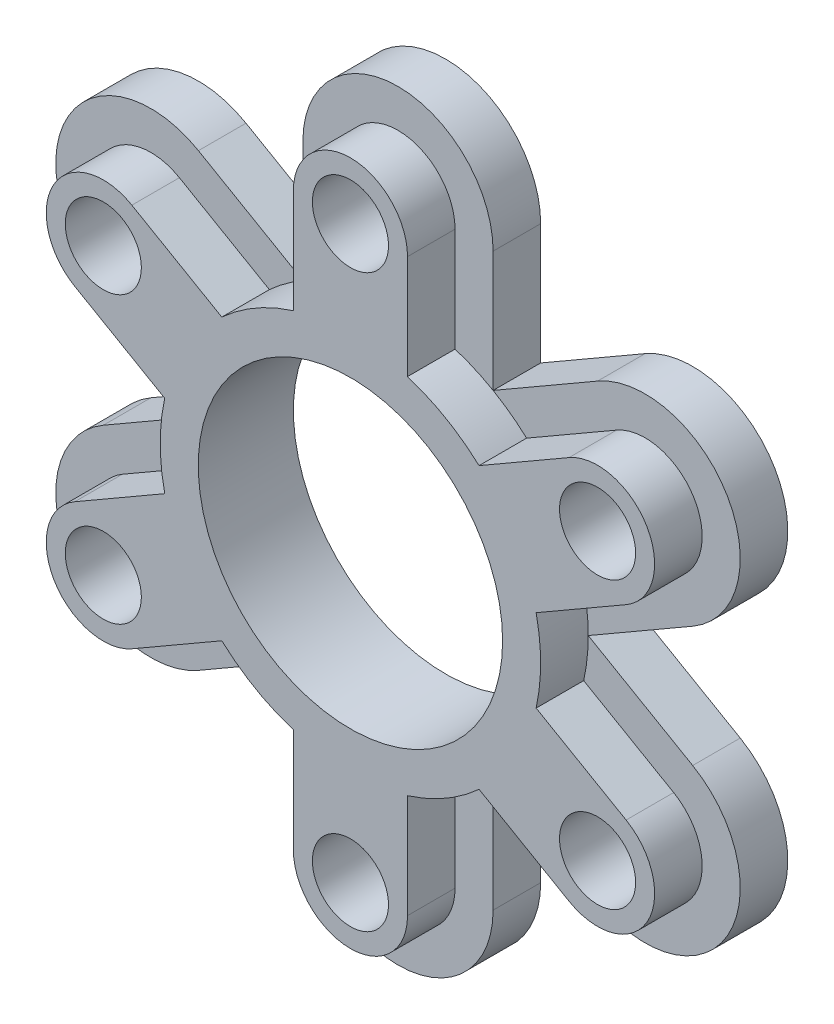
SolidWorks part; units mm, degrees
ref_plane "Front Plane" through (0, 0, 0) normal (0, 0, 1) x (1, 0, 0)
ref_plane "Top Plane" through (0, 0, 0) normal (0, 1, 0) x (1, 0, 0)
ref_plane "Right Plane" through (0, 0, 0) normal (1, 0, 0) x (0, 0, -1)
sketch "Sketch1" plane through (0, 0, 0) normal (0, 0, 1) x (1, 0, 0)
  line L0 (-50.8017, 0) -> (64.1892, 0) construction
  line L1 (-13.9585, 30) -> (15.1705, 30) construction
  line L2 (0, 48.8271) -> (0, -54.1094) construction
  line L3 (-10, 30) -> (-10, 17.3205)
  line L4 (-6, 30) -> (-6, 19.0788)
  line L5 (6, 30) -> (6, 19.0788)
  line L6 (22.9808, 20.1962) -> (13.5227, 14.7355)
  line L7 (10, 30) -> (10, 17.3205)
  line L8 (20.9808, 23.6603) -> (10, 17.3205)
  line L9 (28.9808, 9.8038) -> (19.5227, 4.3432)
  line L10 (30.9808, 6.3397) -> (20, 0)
  line L11 (28.9808, -9.8038) -> (19.5227, -4.3432)
  line L12 (30.9808, -6.3397) -> (20, 0)
  line L13 (22.9808, -20.1962) -> (13.5227, -14.7355)
  line L14 (20.9808, -23.6603) -> (10, -17.3205)
  line L15 (6, -30) -> (6, -19.0788)
  line L16 (10, -30) -> (10, -17.3205)
  line L17 (-6, -30) -> (-6, -19.0788)
  line L18 (-10, -30) -> (-10, -17.3205)
  line L19 (-22.9808, -20.1962) -> (-13.5227, -14.7355)
  line L20 (-20.9808, -23.6603) -> (-10, -17.3205)
  line L21 (-28.9808, -9.8038) -> (-19.5227, -4.3432)
  line L22 (-30.9808, -6.3397) -> (-20, 0)
  line L23 (-28.9808, 9.8038) -> (-19.5227, 4.3432)
  line L24 (-30.9808, 6.3397) -> (-20, 0)
  line L25 (-22.9808, 20.1962) -> (-13.5227, 14.7355)
  line L26 (-20.9808, 23.6603) -> (-10, 17.3205)
  circle A0 centre (0, 0) radius 30 construction
  circle A1 centre (0, 0) radius 16
  circle A2 centre (0, 30) radius 4
  arc A3 (10, 30) -> (-10, 30) centre (0, 30) ccw
  arc A5 (6, 30) -> (-6, 30) centre (0, 30) ccw
  arc A6 (30.9808, 6.3397) -> (20.9808, 23.6603) centre (25.9808, 15) ccw
  arc A7 (28.9808, 9.8038) -> (22.9808, 20.1962) centre (25.9808, 15) ccw
  circle A8 centre (25.9808, 15) radius 4
  arc A9 (20.9808, -23.6603) -> (30.9808, -6.3397) centre (25.9808, -15) ccw
  arc A10 (22.9808, -20.1962) -> (28.9808, -9.8038) centre (25.9808, -15) ccw
  circle A11 centre (25.9808, -15) radius 4
  arc A12 (-10, -30) -> (10, -30) centre (0, -30) ccw
  arc A13 (-6, -30) -> (6, -30) centre (0, -30) ccw
  circle A14 centre (0, -30) radius 4
  arc A15 (-30.9808, -6.3397) -> (-20.9808, -23.6603) centre (-25.9808, -15) ccw
  arc A16 (-28.9808, -9.8038) -> (-22.9808, -20.1962) centre (-25.9808, -15) ccw
  circle A17 centre (-25.9808, -15) radius 4
  arc A18 (-20.9808, 23.6603) -> (-30.9808, 6.3397) centre (-25.9808, 15) ccw
  arc A19 (-22.9808, 20.1962) -> (-28.9808, 9.8038) centre (-25.9808, 15) ccw
  circle A20 centre (-25.9808, 15) radius 4
  arc A21 (-19.5227, 4.3432) -> (-19.5227, -4.3432) centre (0, 0) ccw
  arc A22 (-13.5227, -14.7355) -> (-6, -19.0788) centre (0, 0) ccw
  arc A23 (6, -19.0788) -> (13.5227, -14.7355) centre (0, 0) ccw
  arc A24 (19.5227, -4.3432) -> (19.5227, 4.3432) centre (0, 0) ccw
  arc A25 (13.5227, 14.7355) -> (6, 19.0788) centre (0, 0) ccw
  arc A26 (-6, 19.0788) -> (-13.5227, 14.7355) centre (0, 0) ccw
  dimension "D1" = 60
  dimension "D2" = 32
  dimension "D3" = 8
  dimension "D4" = 10
  dimension "D5" = 6
  dimension "D6" = 6
  dimension "D7" = 20
extrude "Boss-Extrude2" add sketch "Sketch1" along normal blind 10 contours L4 A26 L25 A19 L23 A21 L21 A16 L19 A22 L17 A13 L15 A23 L13 A10 L11 A24 L9 A7 L6 A25 L5 A5 A20 A1 A2 A8 A11 A14 A17 region at (-7.6606, 17.4276, 0)
extrude "Boss-Extrude3" add sketch "Sketch1<4>" along normal blind 5 contours A26 L26 A18 L24 A21 L23 A19 L25 | A26 L4 A5 L5 A25 L7 A3 L3 | A25 L6 A7 L9 A24 L10 A6 L8 | A24 L11 A10 L13 A23 L14 A9 L12 | A23 L15 A13 L17 A22 L18 A12 L16 | A22 L19 A16 L21 A21 L22 A15 L20 region at (0, 39.6976, 0) region at (-12.0455, 16.4152, 0) region at (15.6707, 20.1781, 0) region at (-20.2387, -2.2241, 0) region at (25.3101, -3.4821, 0) region at (-8.1698, -18.586, 0)
sketch "Sketch1<4>" plane through (0, 0, 0) normal (0, 0, 1) x (1, 0, 0) same geometry as "Sketch1"
